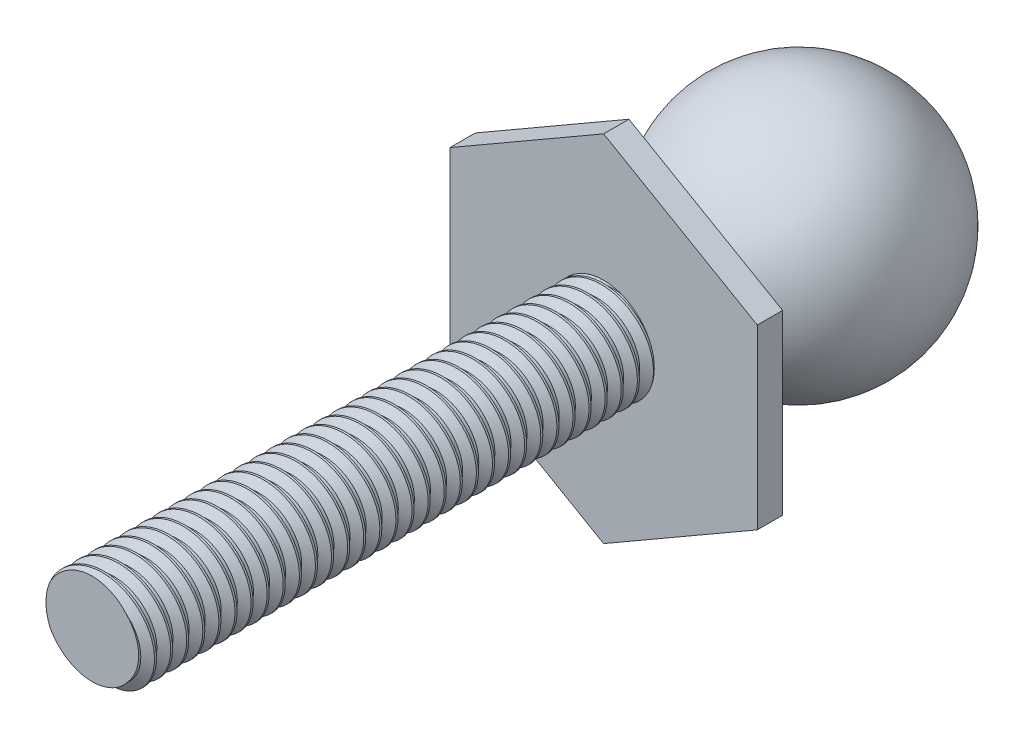
SolidWorks part; units mm, degrees
ref_plane "Front Plane" through (0, 0, 0) normal (0, 0, 1) x (1, 0, 0)
ref_plane "Top Plane" through (0, 0, 0) normal (0, 1, 0) x (1, 0, 0)
ref_plane "Right Plane" through (0, 0, 0) normal (1, 0, 0) x (0, 0, -1)
sketch "Sketch2" plane through (0, 0, 0) normal (0, 1, 0) x (1, 0, 0)
  line L2 (-1, -1.9034) -> (-3.5, -1.9034)
  line L3 (-3.5, -1.9034) -> (-3.5, -2.4034)
  line L4 (-3.5, -2.4034) -> (-1, -2.4034)
  line L5 (-1, -2.4034) -> (-1, -12.4034)
  line L6 (-1, -12.4034) -> (0, -12.4034)
  line L7 (0, 3.9466) -> (0, -12.4034)
  arc A2 (0, 3.9466) -> (-1.1945, -0.7496) centre (0, 1.4466) ccw
  arc A3 (-1.1945, -0.7496) -> (-1, -1.9034) centre (-1.5498, -1.4028) cw
  dimension "D5" = 2.5
  dimension "D1" = 0.5
  dimension "D2" = 1
  dimension "D3" = 10
  dimension "D4" = 2.5
  dimension "16.35" = 16.35
revolve "Revolve2" add sketch "Sketch2" angle 360 about L7
thread "Thread2" pitch 0.3175 profile "Thread Profile2" start angle 0, offset 0.3, length 10.5, pitch 0.3175, diameter 2
ref_plane "Plane2" through (1, 0, 2.1034) normal (0, -1, 0) x (1, 0, 0)
sketch "Thread Profile2" plane through (1, 0, 2.1034) normal (0, -1, 0) x (1, 0, 0)
  line L0 (0, 0) -> (0, 0.3175) construction
  line L11 (0, 0) -> (0, 0.2778)
  line L12 (0, 0.2778) -> (-0.1719, 0.1786)
  line L13 (-0.1719, 0.1786) -> (-0.1719, 0.0992)
  line L15 (-0.1719, 0.0992) -> (0, 0)
  line L17 (-0.1719, 0.1389) -> (0, 0.1389) construction
  point P2 (0, 0)
  dimension "Pitch" = 0.3175
  dimension "Profile_Angle" = 60
  dimension "Profile_Land" = 0.0794
  dimension "Profile_Height" = 0.1719
sketch "Sketch8" plane through (0, 0, 1.9034) normal (0, 0, -1) x (-1, 0, 0)
  line L1 (0, -3.5) -> (3.0311, -1.75)
  line L2 (3.0311, -1.75) -> (3.0311, 1.75)
  line L3 (3.0311, 1.75) -> (0, 3.5)
  line L4 (0, 3.5) -> (-3.0311, 1.75)
  line L5 (-3.0311, 1.75) -> (-3.0311, -1.75)
  line L6 (-3.0311, -1.75) -> (0, -3.5)
  circle A0 centre (0, 0) radius 3.0311 construction
extrude "Cut-Extrude1" cut sketch "Sketch8" against normal blind 10 flip side to cut
